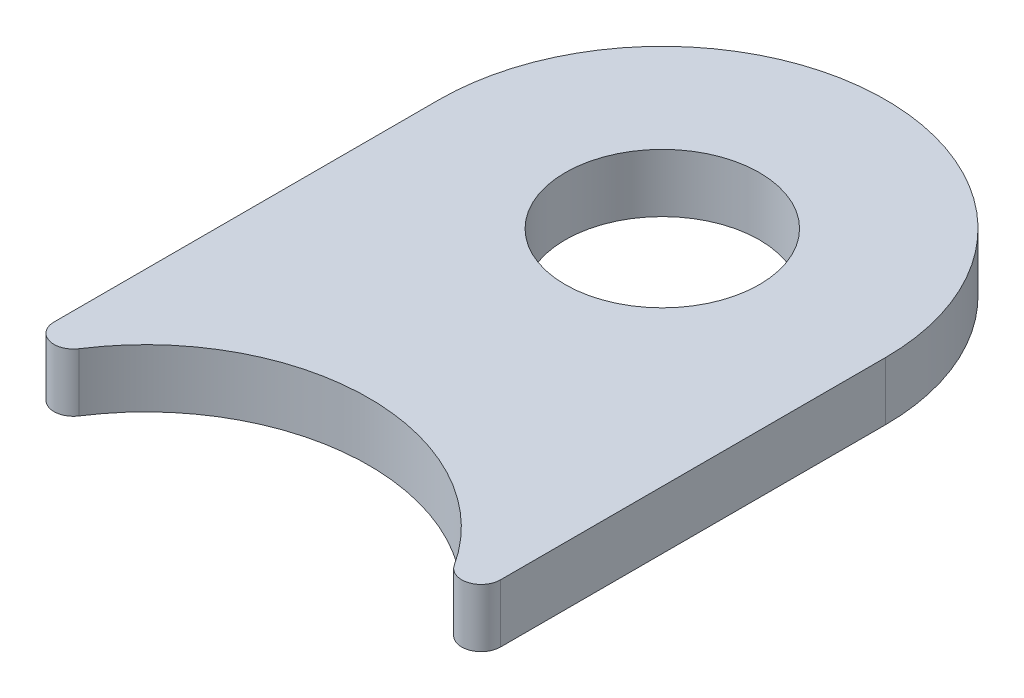
SolidWorks part; units mm, degrees
ref_plane "Front Plane" through (0, 0, 0) normal (0, 0, 1) x (1, 0, 0)
ref_plane "Top Plane" through (0, 0, 0) normal (0, 1, 0) x (1, 0, 0)
ref_plane "Right Plane" through (0, 0, 0) normal (1, 0, 0) x (0, 0, -1)
sketch "Sketch1" plane through (0, 0, 0) normal (0, 1, 0) x (1, 0, 0)
  line L0 (-11.5, 26.6146) -> (-11.5, 0)
  line L1 (11.5, 26.6146) -> (11.5, 0)
  line L2 (-11.5, 0) -> (11.5, 0)
  circle A0 centre (0, 0) radius 11.5
  circle A1 centre (0, 26.6146) radius 11.5
  circle A2 centre (0, 26.6146) radius 5
  dimension "D1" = 10
  dimension "D2" = 23
extrude "Boss-Extrude1" add sketch "Sketch1" along normal blind 3 contours A1 L0 A0 L1 | A1 A2 region at (0, 0, -13.3073) region at (0, 0, -37.7893)
fillet "Fillet1" radius 1 2 edges at (-11.5, 1.5, 0) (11.5, 1.5, 0)
